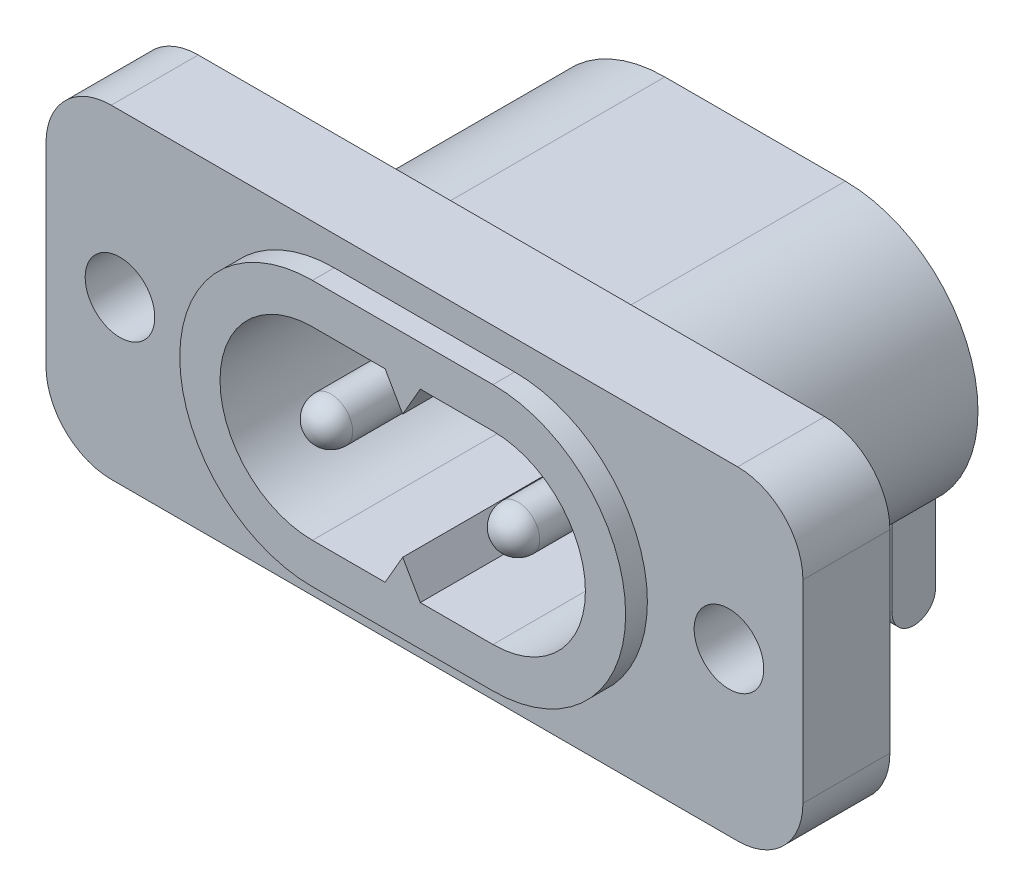
SolidWorks part; units mm, degrees
ref_plane "Front Plane" through (0, 0, 0) normal (0, 0, 1) x (1, 0, 0)
ref_plane "Top Plane" through (0, 0, 0) normal (0, 1, 0) x (1, 0, 0)
ref_plane "Right Plane" through (0, 0, 0) normal (1, 0, 0) x (0, 0, -1)
sketch "Sketch1" plane through (0, 0, 0) normal (0, 0, 1) x (1, 0, 0)
  line L0 (0, 10.1366) -> (0, -10.1366) construction
  line L1 (-14.4, 7.45) -> (14.4, 7.45)
  line L2 (-17.4, 4.45) -> (-17.4, -4.45)
  line L3 (-14.4, -7.45) -> (14.4, -7.45)
  line L4 (17.4, 4.45) -> (17.4, -4.45)
  line L5 (-17.4, 7.45) -> (17.4, -7.45) construction
  line L6 (-17.4, -7.45) -> (17.4, 7.45) construction
  line L7 (-4.15, 4.25) -> (-0.8083, 4.25)
  line L8 (-0.8083, 4.25) -> (0, 2.85)
  line L9 (0, 0) -> (-17.8389, 0) construction
  line L10 (-4.15, -4.25) -> (-0.8083, -4.25)
  line L11 (-0.8083, -4.25) -> (0, -2.85)
  line L12 (0.8083, -4.25) -> (0, -2.85)
  line L13 (4.15, -4.25) -> (0.8083, -4.25)
  line L14 (4.15, 4.25) -> (0.8083, 4.25)
  line L15 (0.8083, 4.25) -> (0, 2.85)
  line L16 (-8.4, 0) -> (-8.4, -5.471) construction
  arc A0 (14.4, 7.45) -> (17.4, 4.45) centre (14.4, 4.45) cw
  arc A1 (17.4, -4.45) -> (14.4, -7.45) centre (14.4, -4.45) cw
  arc A2 (-17.4, -4.45) -> (-14.4, -7.45) centre (-14.4, -4.45) ccw
  arc A3 (-17.4, 4.45) -> (-14.4, 7.45) centre (-14.4, 4.45) cw
  circle A4 centre (14, 0) radius 1.6
  circle A5 centre (-14, 0) radius 1.6
  arc A6 (-4.15, 4.25) -> (-4.15, -4.25) centre (-4.15, 0) ccw
  arc A7 (4.15, 4.25) -> (4.15, -4.25) centre (4.15, 0) cw
  point P0 (0, 0)
  dimension "D2" = 3
  dimension "D4" = 3.2
  dimension "D6" = 60
  dimension "D1" = 14.9
  dimension "D3" = 34.8
  dimension "D5" = 14
  dimension "D7" = 8.4
  dimension "D8" = 8.5
  dimension "D9" = 1.4
extrude "Boss-Extrude1" add sketch "Sketch1" along normal mid plane 4
sketch "Sketch2" plane through (0, 0, 2) normal (0, 0, 1) x (1, 0, 0)
  line L0 (-4.15, 0) -> (4.15, 0) construction
  line L1 (-4.15, 6.1) -> (4.15, 6.1)
  line L2 (-4.15, -6.1) -> (4.15, -6.1)
  line L3 (10.25, 0) -> (10.25, 12.2074) construction
  line L4 (-10.25, 0) -> (-10.25, 12.8806) construction
  line L5 (-0.8083, 4.25) -> (-4.15, 4.25) construction
  line L6 (0.8083, 4.25) -> (0, 2.85) construction
  line L7 (0, 2.85) -> (-0.8083, 4.25) construction
  line L8 (4.15, 4.25) -> (0.8083, 4.25) construction
  line L9 (0.8083, -4.25) -> (4.15, -4.25) construction
  line L10 (0, -2.85) -> (0.8083, -4.25) construction
  line L11 (-0.8083, -4.25) -> (0, -2.85) construction
  line L12 (-4.15, -4.25) -> (-0.8083, -4.25) construction
  line L13 (0.8083, 4.25) -> (0, 2.85)
  line L14 (4.15, 4.25) -> (0.8083, 4.25)
  line L15 (0.8083, -4.25) -> (4.15, -4.25)
  line L16 (0, -2.85) -> (0.8083, -4.25)
  line L17 (-0.8083, -4.25) -> (0, -2.85)
  line L18 (-4.15, -4.25) -> (-0.8083, -4.25)
  line L19 (-0.8083, 4.25) -> (-4.15, 4.25)
  line L20 (0, 2.85) -> (-0.8083, 4.25)
  arc A0 (-4.15, 6.1) -> (-4.15, -6.1) centre (-4.15, 0) ccw
  arc A1 (4.15, -6.1) -> (4.15, 6.1) centre (4.15, 0) ccw
  arc A2 (-4.15, 4.25) -> (-4.15, -4.25) centre (-4.15, 0) ccw construction
  arc A3 (4.15, -4.25) -> (4.15, 4.25) centre (4.15, 0) ccw construction
  arc A4 (4.15, -4.25) -> (4.15, 4.25) centre (4.15, 0) ccw
  arc A5 (-4.15, 4.25) -> (-4.15, -4.25) centre (-4.15, 0) ccw
  point P3 (0, 0)
  dimension "D1" = 20.5
  dimension "D2" = 12.2
extrude "Boss-Extrude2" add sketch "Sketch2" along normal blind 1 and the other way blind 15.2
sketch "Sketch3" plane through (0, 0, 3) normal (0, 0, 1) x (1, 0, 0)
  line L0 (0.8083, 4.25) -> (0, 2.85) construction
  line L1 (4.15, 4.25) -> (0.8083, 4.25) construction
  line L2 (0.8083, -4.25) -> (4.15, -4.25) construction
  line L3 (0, -2.85) -> (0.8083, -4.25) construction
  line L4 (-0.8083, -4.25) -> (0, -2.85) construction
  line L5 (-4.15, -4.25) -> (-0.8083, -4.25) construction
  line L6 (-0.8083, 4.25) -> (-4.15, 4.25) construction
  line L7 (0, 2.85) -> (-0.8083, 4.25) construction
  line L8 (0.8083, 4.25) -> (0, 2.85)
  line L9 (4.15, 4.25) -> (0.8083, 4.25)
  line L10 (0.8083, -4.25) -> (4.15, -4.25)
  line L11 (0, -2.85) -> (0.8083, -4.25)
  line L12 (-0.8083, -4.25) -> (0, -2.85)
  line L13 (-4.15, -4.25) -> (-0.8083, -4.25)
  line L14 (-0.8083, 4.25) -> (-4.15, 4.25)
  line L15 (0, 2.85) -> (-0.8083, 4.25)
  arc A0 (4.15, -4.25) -> (4.15, 4.25) centre (4.15, 0) ccw construction
  arc A1 (-4.15, 4.25) -> (-4.15, -4.25) centre (-4.15, 0) ccw construction
  arc A2 (4.15, -4.25) -> (4.15, 4.25) centre (4.15, 0) ccw
  arc A3 (-4.15, 4.25) -> (-4.15, -4.25) centre (-4.15, 0) ccw
extrude "Boss-Extrude3" add sketch "Sketch3" along normal blind 1 from offset 9.8 offset against normal yes
sketch "Sketch4" plane through (0, 0, 0) normal (1, 0, 0) x (0, 0, -1)
  line L0 (0, 0) -> (13.8, 0) construction
  line L1 (13.2, 1) -> (15.8, 1)
  line L2 (13.2, -6.1) -> (13.2, 6.1) construction
  line L3 (15.8, 1) -> (15.8, -10.62)
  line L4 (13.8, -10.62) -> (13.8, -1)
  line L5 (13.8, -1) -> (13.2, -1)
  line L6 (13.2, -1) -> (13.2, 1)
  line L7 (-3, 6.1) -> (-3, -6.1) construction
  line L8 (-1.9966, -7.45) -> (4.5753, -7.45) construction
  line L9 (-2, -7.45) -> (2, -7.45) construction
  line L10 (14.8, -11.62) -> (11.4728, -11.62) construction
  line L11 (13.8, -1) -> (18.5, -1) construction
  line L12 (18.5, -1) -> (18.5, 1) construction
  line L13 (18.5, 1) -> (15.8, 1) construction
  line L14 (-3, 6.1) -> (-3, -6.1) construction
  arc A0 (15.8, -10.62) -> (13.8, -10.62) centre (14.8, -10.62) cw
  dimension "D1" = 18.8
  dimension "D2" = 2.6
  dimension "D3" = 4.17
  dimension "D4" = 2
  dimension "D5" = 2
  dimension "D6" = 21.5
extrude "Boss-Extrude4" add sketch "Sketch4" against normal mid plane 1 from offset 5.2 separate body
sketch "Sketch5" plane through (0, 0, -13.2) normal (0, 0, -1) x (-1, 0, 0)
  line L2 (4.15, 6.1) -> (-4.15, 6.1)
  line L3 (-4.15, -6.1) -> (4.15, -6.1)
  line L4 (4.15, 6.1) -> (-4.15, 6.1)
  line L5 (-4.15, -6.1) -> (4.15, -6.1)
  arc A2 (4.15, -6.1) -> (4.15, 6.1) centre (4.15, 0) ccw
  arc A3 (-4.15, 6.1) -> (-4.15, -6.1) centre (-4.15, 0) ccw
  arc A4 (4.15, -6.1) -> (4.15, 6.1) centre (4.15, 0) ccw
  arc A5 (-4.15, 6.1) -> (-4.15, -6.1) centre (-4.15, 0) ccw
  dimension "D1" = 0
extrude "Boss-Extrude6" add sketch "Sketch5" against normal blind 1
mirror "Mirror2" about plane through (0, 0, 0) normal (1, 0, 0) of "Boss-Extrude4"
sketch "Sketch6" plane through (0, 0, -5.8) normal (0, 0, 1) x (1, 0, 0)
  line L0 (0, 2.85) -> (0, -2.85) construction
  circle A0 centre (-4.3, 0) radius 1
  circle A1 centre (4.3, 0) radius 1
  dimension "D1" = 2
  dimension "D2" = 8.6
extrude "Boss-Extrude7" add sketch "Sketch6" along normal up to surface (8.8 mm away) up to face at (0, 0, 3)
fillet "Fillet1" radius 1 2 edges at (5.3, 0, 3) (-3.3, 0, 3)
